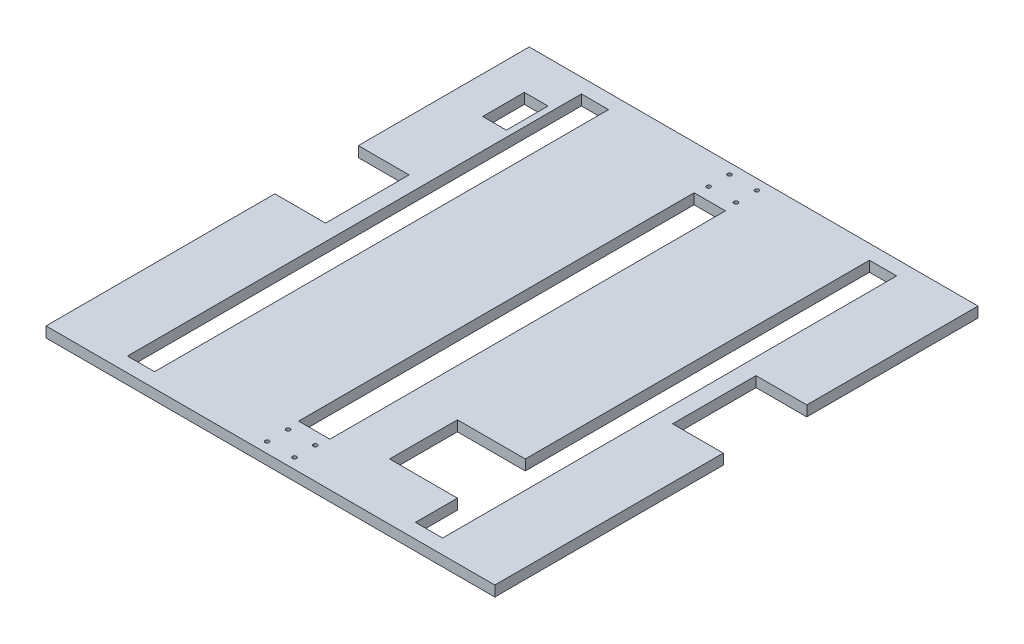
SolidWorks part; units mm, degrees
ref_plane "Front Plane" through (0, 0, 0) normal (0, 0, 1) x (1, 0, 0)
ref_plane "Top Plane" through (0, 0, 0) normal (0, 1, 0) x (1, 0, 0)
ref_plane "Right Plane" through (0, 0, 0) normal (1, 0, 0) x (0, 0, -1)
sketch "Sketch1" plane through (0, 0, 0) normal (0, 1, 0) x (1, 0, 0)
  line L1 (5911.0841, -8489.3124) -> (6341.0841, -8489.3124)
  line L2 (5911.0841, -8489.3124) -> (5911.0841, -8952.3124)
  line L3 (5911.0841, -8952.3124) -> (6341.0841, -8952.3124)
  line L4 (6341.0841, -8489.3124) -> (6341.0841, -8952.3124)
  dimension "D1" = 463
  dimension "D2" = 430
extrude "Boss-Extrude1" add sketch "Sketch1" along normal blind 10
sketch "Sketch2" plane through (0, 10, 0) normal (0, 1, 0) x (1, 0, 0)
  line L0 (5911.0841, -8489.3124) -> (5911.0841, -8952.3124) construction
  line L1 (5959.6841, -8733.0598) -> (5911.0841, -8733.0598)
  line L2 (5959.6841, -8733.0598) -> (5959.6841, -8653.0598)
  line L3 (5959.6841, -8653.0598) -> (5911.0841, -8653.0598)
  line L4 (5911.0841, -8733.0598) -> (5911.0841, -8653.0598)
  line L9 (6341.0841, -8952.3124) -> (6341.0841, -8489.3124) construction
  line L10 (6341.0841, -8733.3844) -> (6292.4841, -8733.3844)
  line L11 (6341.0841, -8733.3844) -> (6341.0841, -8653.3844)
  line L12 (6341.0841, -8653.3844) -> (6292.4841, -8653.3844)
  line L13 (6292.4841, -8733.3844) -> (6292.4841, -8653.3844)
  dimension "D1" = 48.6
  dimension "D2" = 80
  dimension "D3" = 80
  dimension "D4" = 48.6
extrude "Cut-Extrude1" cut sketch "Sketch2" against normal blind 10
sketch "Sketch3" plane through (0, 10, 0) normal (0, 1, 0) x (1, 0, 0)
  line L0 (5975.0841, -8541.6519) -> (5975.0841, -8938.3124)
  line L1 (6277.0841, -8938.3124) -> (6251.0841, -8938.3124)
  line L2 (6277.0841, -8938.3124) -> (6277.0841, -8503.3124)
  line L3 (6277.0841, -8503.3124) -> (6251.0841, -8503.3124)
  line L4 (6251.0841, -8938.3124) -> (6251.0841, -8503.3124)
  line L5 (5975.0841, -8503.3124) -> (6001.0841, -8503.3124)
  line L11 (5975.0841, -8938.3124) -> (6001.0841, -8938.3124)
  line L12 (6001.0841, -8503.3124) -> (6001.0841, -8938.3124)
  line L33 (5946.4841, -8529.3124) -> (5969.1312, -8529.3124)
  line L34 (5946.4841, -8529.3124) -> (5946.4841, -8569.3124)
  line L35 (5946.4841, -8569.3124) -> (5969.1312, -8569.3124)
  line L36 (5911.0841, -8733.0598) -> (5911.0841, -8952.3124) construction
  line L37 (6341.0841, -8952.3124) -> (6341.0841, -8733.3844) construction
  line L38 (5969.1312, -8529.3124) -> (5969.1312, -8569.3124)
  line L39 (6111.0841, -8531.3124) -> (6141.0841, -8531.3124)
  line L40 (6111.0841, -8531.3124) -> (6111.0841, -8910.3124)
  line L41 (6111.0841, -8910.3124) -> (6141.0841, -8910.3124)
  line L42 (6141.0841, -8531.3124) -> (6141.0841, -8910.3124)
  line L44 (6341.0841, -8489.3124) -> (5911.0841, -8489.3124) construction
  line L45 (5975.0841, -8503.3124) -> (5975.0841, -8541.6519)
  line L47 (5911.0841, -8952.3124) -> (6341.0841, -8952.3124) construction
  circle A0 centre (6112.9841, -8942.3124) radius 1.9
  circle A1 centre (6139.1841, -8942.3124) radius 1.9
  circle A2 centre (6112.9841, -8499.3124) radius 1.9
  circle A3 centre (6139.1841, -8499.3124) radius 1.9
  circle A4 centre (6112.9841, -8922.3124) radius 1.9
  circle A5 centre (6139.1841, -8922.3124) radius 1.9
  circle A6 centre (6112.9841, -8519.3124) radius 1.9
  circle A7 centre (6139.1841, -8519.3124) radius 1.9
  point P32 (6126.0841, -8489.3124)
  point P33 (6126.0841, -8531.3124)
  dimension "D12" = 10
  dimension "D13" = 10
  dimension "D15" = 42
  dimension "D16" = 20
  dimension "D18" = 20
  dimension "D1" = 26
  dimension "D2" = 435
  dimension "D3" = 26
  dimension "D4" = 435
  dimension "D5" = 10
  dimension "D6" = 64
  dimension "D7" = 40
  dimension "D8" = 64
  dimension "D9" = 30
  dimension "D10" = 379
  dimension "D11" = 110
  dimension "D14" = 10
  dimension "D17" = 20
  dimension "D19" = 20
  dimension "D20" = 14
  dimension "D21" = 14
extrude "Cut-Extrude2" cut sketch "Sketch3" against normal blind 10
sketch "Sketch4" plane through (0, 10, 0) normal (0, 1, 0) x (1, 0, 0)
  line L0 (6251.0841, -8503.3124) -> (6251.0841, -8938.3124) construction
  line L1 (6251.0841, -8898.0965) -> (6186.0841, -8898.0965)
  line L2 (6251.0841, -8898.0965) -> (6251.0841, -8833.0965)
  line L3 (6251.0841, -8833.0965) -> (6186.0841, -8833.0965)
  line L4 (6186.0841, -8898.0965) -> (6186.0841, -8833.0965)
  dimension "D1" = 65
  dimension "D2" = 65
extrude "Cut-Extrude3" cut sketch "Sketch4" against normal blind 10
ref_plane "Plane1" through (6126.0841, 0, 0) normal (-1, 0, 0) x (0, 0, 1)
sketch "Sketch5" plane through (6126.0841, 0, 0) normal (-1, 0, 0) x (0, 0, 1)
  line L1 (8395.6862, 142.8464) -> (9031.9061, 142.8464)
  line L2 (8395.6862, 142.8464) -> (8395.6862, -229.0644)
  line L3 (8395.6862, -229.0644) -> (9031.9061, -229.0644)
  line L4 (9031.9061, 142.8464) -> (9031.9061, -229.0644)
